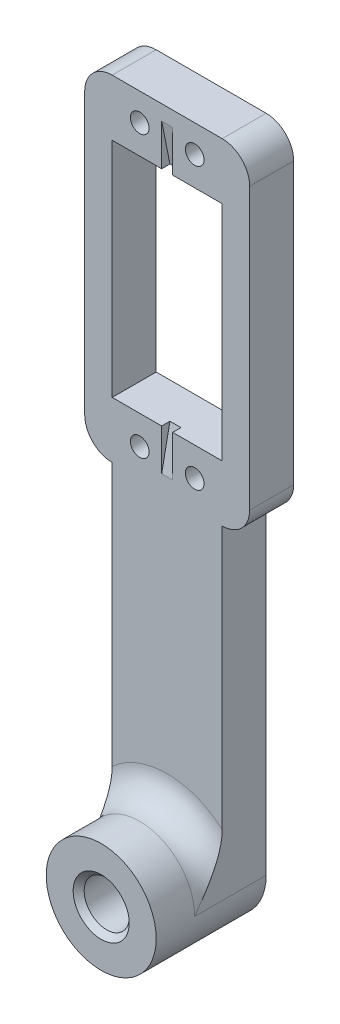
SolidWorks part; units mm, degrees
note: The reader was unsure of these and kept them because the rebuilt part matched: shared geometry of "Эскиз1<3>".
ref_plane "Спереди" through (0, 0, 0) normal (0, 0, 1) x (1, 0, 0)
ref_plane "Сверху" through (0, 0, 0) normal (0, 1, 0) x (1, 0, 0)
ref_plane "Справа" through (0, 0, 0) normal (1, 0, 0) x (0, 0, -1)
sketch "Эскиз1" plane through (0, 0, 0) normal (0, 0, 1) x (1, 0, 0)
  line L0 (0, 0) -> (0, 100) construction
  line L1 (-10, 59) -> (-10, 0)
  line L2 (10, 59) -> (10, 0)
  line L3 (-10, 89.5) -> (10, 89.5) construction
  line L4 (-15, 120) -> (15, 120)
  line L5 (-15, 120) -> (-15, 59)
  line L6 (-15, 59) -> (15, 59)
  line L7 (15, 120) -> (15, 59)
  line L8 (-10, 109.75) -> (10, 109.75)
  line L9 (-10, 109.75) -> (-10, 69.25)
  line L10 (-10, 69.25) -> (10, 69.25)
  line L11 (10, 109.75) -> (10, 69.25)
  circle A0 centre (0, 0) radius 10
  circle A1 centre (0, 100) radius 5
  circle A2 centre (0, 0) radius 4.1
  circle A3 centre (-5, 115) radius 1.7
  circle A4 centre (5, 115) radius 1.7
  circle A5 centre (5, 64) radius 1.7
  circle A6 centre (-5, 64) radius 1.7
  dimension "D2" = 20
  dimension "D3" = 8.2
  dimension "D7" = 10
  dimension "D11" = 3.4
  dimension "D1" = 100
  dimension "D4" = 30
  dimension "D6" = 20
  dimension "D8" = 9.75
  dimension "D9" = 40.5
  dimension "D10" = 20
  dimension "D12" = 10
  dimension "D13" = 15
extrude "Бобышка-Вытянуть1" add sketch "Эскиз1" along normal blind 8
extrude "Бобышка-Вытянуть2" add sketch "Эскиз1<3>" along normal blind 20
sketch "Эскиз1<3>" plane through (0, 0, 0) normal (0, 0, 1) x (1, 0, 0) same geometry as "Эскиз1"
fillet "Скругление1" radius 5 4 edges at (15, 59, 4) (-15, 59, 4) (-15, 120, 4) (15, 120, 4)
sketch "Эскиз3" plane through (0, 0, 0) normal (1, 0, 0) x (0, 0, -1)
  line L0 (-8, 109.75) -> (-8, 69.25) construction
  line L1 (-8, 109.75) -> (-8, 69.25)
  line L2 (-8, 109.75) -> (-8, 117.25)
  line L3 (-8, 117.25) -> (-6.5, 109.75)
  line L4 (-6.5, 109.75) -> (-8, 109.75)
  line L5 (-8, 89.5) -> (4.2874, 89.5) construction
  line L6 (-8, 69.25) -> (-8, 61.75)
  line L7 (-8, 61.75) -> (-6.5, 69.25)
  line L8 (-6.5, 69.25) -> (-8, 69.25)
  dimension "D1" = 7.5
  dimension "D2" = 1.5
extrude "Вырез-уголки сервы" cut sketch "Эскиз3" against normal mid plane 2 contours L4 L3 L2 | L7 L8 L6
sketch "Эскиз4" plane through (0, 0, 0) normal (0, 0, -1) x (-1, 0, 0)
  line L0 (0, 0) -> (0, 17.4) construction
  line L1 (-2.6, 17.4) -> (-4.6613, 4.3855)
  line L2 (2.6, 17.4) -> (4.6613, 4.3855)
  circle A0 centre (0, 0) radius 6.4
  circle A1 centre (0, 17.4) radius 2.6
  dimension "D2" = 12.8
  dimension "D3" = 5.2
  dimension "D1" = 17.4
  dimension "D4" = 18
extrude "Вырез-Носик сервы" cut sketch "Эскиз4" against normal blind 4
chamfer "Фаска1" distance 1 angle 45 2 edges at (4.1, 0, 20) (-4.1, 0, 4)
sketch "Эскиз5" plane through (0, 0, 0) normal (0, 0, -1) x (-1, 0, 0)
  line L1 (-6.7321, 118) -> (-8.4641, 115)
  line L2 (-8.4641, 115) -> (-6.7321, 112)
  line L3 (-6.7321, 112) -> (-3.2679, 112)
  line L4 (-3.2679, 112) -> (-1.5359, 115)
  line L5 (-1.5359, 115) -> (-3.2679, 118)
  line L6 (-3.2679, 118) -> (-6.7321, 118)
  line L7 (3.2679, 118) -> (1.5359, 115)
  line L8 (1.5359, 115) -> (3.2679, 112)
  line L9 (3.2679, 112) -> (6.7321, 112)
  line L10 (6.7321, 112) -> (8.4641, 115)
  line L11 (8.4641, 115) -> (6.7321, 118)
  line L12 (6.7321, 118) -> (3.2679, 118)
  line L13 (-6.7321, 67) -> (-8.4641, 64)
  line L14 (-8.4641, 64) -> (-6.7321, 61)
  line L15 (-6.7321, 61) -> (-3.2679, 61)
  line L16 (-3.2679, 61) -> (-1.5359, 64)
  line L17 (-1.5359, 64) -> (-3.2679, 67)
  line L18 (-3.2679, 67) -> (-6.7321, 67)
  line L19 (8.4641, 64) -> (6.7321, 67)
  line L20 (6.7321, 67) -> (3.2679, 67)
  line L21 (3.2679, 67) -> (1.5359, 64)
  line L22 (1.5359, 64) -> (3.2679, 61)
  line L23 (3.2679, 61) -> (6.7321, 61)
  line L24 (6.7321, 61) -> (8.4641, 64)
  circle A0 centre (5, 115) radius 1.7 construction
  circle A1 centre (-5, 115) radius 1.7 construction
  circle A2 centre (-5, 64) radius 1.7 construction
  circle A3 centre (5, 64) radius 1.7 construction
  circle A4 centre (5, 115) radius 1.7
  circle A5 centre (-5, 115) radius 1.7
  circle A6 centre (-5, 64) radius 1.7
  circle A7 centre (5, 64) radius 1.7
  circle A8 centre (-5, 115) radius 3 construction
  circle A9 centre (5, 115) radius 3 construction
  circle A10 centre (-5, 64) radius 3 construction
  circle A11 centre (5, 64) radius 3 construction
  dimension "D1" = 6
extrude "Вырез-Вытянуть1" cut sketch "Эскиз5" against normal blind 4
fillet "Скругление2" radius 5 1 edges at (0, 10, 8)
